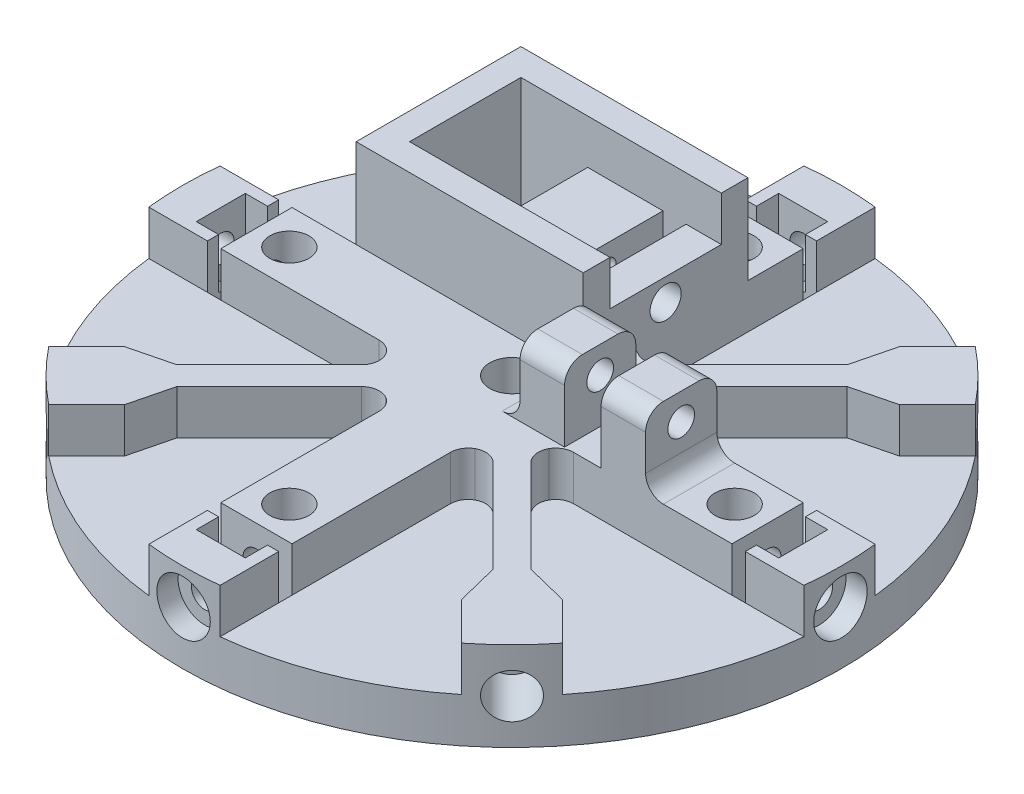
SolidWorks part; units mm, degrees
material "Custom Plastic"
ref_plane "Front Plane" through (0, 0, 0) normal (0, 0, 1) x (1, 0, 0)
ref_plane "Top Plane" through (0, 0, 0) normal (0, 1, 0) x (1, 0, 0)
ref_plane "Right Plane" through (0, 0, 0) normal (1, 0, 0) x (0, 0, -1)
sketch "Sketch1" plane through (0, 0, 0) normal (0, 1, 0) x (1, 0, 0)
  circle A0 centre (0, 0) radius 37
  circle A1 centre (0, 0) radius 2.5
  dimension "D1" = 74
  dimension "D2" = 5
extrude "Boss-Extrude1" add sketch "Sketch1" along normal blind 10
sketch "Sketch5" plane through (0, 10, 0) normal (0, 1, 0) x (1, 0, 0)
  circle A0 centre (0, 0) radius 25 construction
  circle A1 centre (0, 0) radius 37 construction
  point P3 (0, 25)
  point P6 (0, 37)
  point P7 (25, 0)
  point P8 (0, -25)
  point P9 (-25, 0)
  dimension "D1" = 12
  dimension "D2" = 4
hole_wizard "Ø4.0mm Dowel Hole2" positions "Sketch6" profile "Sketch7" hole size "Ø4.0" standard "ANSI Metric"
sketch "Sketch6" plane through (0, 10, 0) normal (0, 1, 0) x (1, 0, 0)
  point P0 (0, 25)
  point P3 (25, 0)
  point P6 (0, -25)
  point P9 (-25, 0)
sketch "Sketch7" plane through (0, 10, -25) normal (1, 0, 0) x (0, 0, 1)
  line L0 (0, 0) -> (0, 9.999)
  line L1 (0, 9.999) -> (2.2, 9.999)
  line L2 (2.2, 9.999) -> (2.2, 0)
  line L5 (2.2, 0) -> (0, 0)
  line L10 (0, 9.999) -> (-2.2, 9.999) construction
  line L11 (0, -6.35) -> (0, 107.95) construction
  dimension "Hole Dia." = 4.4
  dimension "Hole Depth" = 9.999
  dimension "Drill Angle" = 180
ref_plane "Plane1" through (37, 0, 0) normal (1, 0, 0) x (0, 0, -1)
hole_wizard "CBORE for M6 Hex Head Bolt4" positions "Sketch10" profile "Sketch11" counterbore size "M6" standard "ANSI Metric"
sketch "Sketch10" plane through (37, 0, 0) normal (1, 0, 0) x (0, 0, -1)
  point P0 (0, 6)
  dimension "D1" = 6
sketch "Sketch11" plane through (37, 6, 0) normal (0, 1, 0) x (0, 0, -1)
  line L0 (0, 0) -> (0, 11)
  line L1 (0, 11) -> (1.5, 11)
  line L2 (1.5, 11) -> (1.5, 2.5)
  line L3 (1.5, 2.5) -> (3, 2.5)
  line L4 (3, 2.5) -> (3, 0)
  line L5 (3, 0) -> (0, 0)
  line L10 (0, 11) -> (-1.5, 11) construction
  line L11 (0, -6.35) -> (0, 107.95) construction
  dimension "Hole Dia." = 3
  dimension "Hole Depth" = 11
  dimension "C'Bore Dia." = 6
  dimension "C'Bore Depth" = 2.5
  dimension "Drill Angle" = 180
pattern_circular "CirPattern1" count 4 over 360 about axis through (0, 0, 0) along (0, 1, 0) of "CBORE for M6 Hex Head Bolt4"
ref_plane "Plane2" through (26.163, 0, 26.163) normal (0.7071, 0, 0.7071) x (0, -1, 0)
sketch "Sketch18" plane through (26.163, 0, 26.163) normal (0.7071, 0, 0.7071) x (0, -1, 0)
  line L0 (0, 0) -> (-10, 0) construction
  line L1 (-10, 37) -> (-10, -37) construction
  circle A0 centre (-5, 0) radius 2.5
  dimension "D1" = 5
extrude "Cut-Extrude2" cut sketch "Sketch18" against normal blind 6.5
sketch "Sketch19" plane through (0, 10, 0) normal (0, 1, 0) x (1, 0, 0)
  line L0 (-36.7831, -4) -> (-9.6569, -4)
  line L1 (-21.0599, -15.403) -> (-28.838, -23.1812)
  line L2 (-37, 0) -> (0, 0) construction
  line L3 (0, 0) -> (-26.163, -26.163) construction
  line L5 (-4, -36.7831) -> (-4, -9.6569)
  line L7 (-21.0599, -15.403) -> (-15.403, -21.0599)
  line L8 (-15.403, -21.0599) -> (-23.1812, -28.838)
  circle A0 centre (0, 0) radius 37 construction
  arc A1 (-36.7831, -4) -> (-28.838, -23.1812) centre (0, 0) ccw
  arc A2 (-4, -36.7831) -> (-23.1812, -28.838) centre (0, 0) cw
  arc A3 (-9.6569, -4) -> (-4, -9.6569) centre (0, 0) ccw
  point P15 (-18.2314, -18.2314)
  dimension "D1" = 4
  dimension "D2" = 45
  dimension "D3" = 4
  dimension "D4" = 11
extrude "Cut-Extrude3" cut sketch "Sketch19" against normal blind 5
pattern_circular "CirPattern4" count 4 every 90 about axis through (0, 0, 0) along (0, 1, 0) of "Cut-Extrude3"
sketch "Sketch12" plane through (0, 10, 0) normal (0, 1, 0) x (1, 0, 0)
  line L1 (-18.5, 7) -> (-18.5, 19.5)
  line L3 (4, 19.5) -> (4, 7)
  line L4 (-2.55, 7) -> (-2.55, 19.5)
  line L5 (0.05, 7) -> (0.05, 19.5)
  line L6 (-18.5, 19.5) -> (-2.55, 19.5)
  line L7 (4, 19.5) -> (0.05, 19.5)
  line L8 (-2.55, 19.5) -> (0.05, 19.5) construction
  line L9 (-2.55, 7) -> (0.05, 7) construction
  line L10 (0.05, 7) -> (4, 7)
  line L11 (-18.5, 7) -> (-2.55, 7)
  line L12 (4, 13.25) -> (13.5, 13.25) construction
  line L14 (-18.5, 13.25) -> (4, 13.25) construction
  dimension "D1" = 22.5
  dimension "D2" = 15.95
  dimension "D3" = 2.6
  dimension "D4" = 12.5
  dimension "D5" = 9.5
  dimension "D6" = 4
  dimension "D7" = 7
extrude "Boss-Extrude2" add sketch "Sketch12" along normal blind 5 and the other way up to surface other way up to face at (-18.1783, 5, -18.1783)
hole_wizard "CBORE for M5 Hex Head Bolt1" positions "Sketch13" profile "Sketch15" counterbore size "M5" standard "ANSI Metric"
sketch "Sketch13" plane through (4, 0, 0) normal (1, 0, 0) x (0, 0, -1)
  line L0 (13.25, 15) -> (13.25, 10) construction
  line L1 (7, 15) -> (19.5, 15) construction
  line L4 (7, 12.5) -> (19.5, 12.5) construction
  line L5 (7, 15) -> (7, 10) construction
  line L6 (19.5, 15) -> (19.5, 10) construction
  point P0 (13.25, 12.5)
sketch "Sketch15" plane through (4, 12.5, -13.25) normal (0, 1, 0) x (0, 0, -1)
  line L0 (0, 0) -> (0, 12)
  line L1 (0, 12) -> (1, 12)
  line L2 (1, 12) -> (1, 5)
  line L3 (1, 5) -> (1.75, 5)
  line L4 (1.75, 5) -> (1.75, 0)
  line L5 (1.75, 0) -> (0, 0)
  line L10 (0, 12) -> (-1, 12) construction
  line L11 (0, -6.35) -> (0, 107.95) construction
  dimension "Hole Dia." = 2
  dimension "Hole Depth" = 12
  dimension "C'Bore Dia." = 3.5
  dimension "C'Bore Depth" = 5
  dimension "Drill Angle" = 180
sketch "Sketch16" plane through (0, 10, 0) normal (0, 1, 0) x (1, 0, 0)
  line L5 (-18.5, 7) -> (-2.55, 7) construction
  line L11 (4, 4) -> (-21.5, 4)
  line L16 (4, 4) -> (4, 7)
  line L17 (4, 22.5) -> (-21.5, 22.5)
  line L18 (-21.5, 4) -> (-21.5, 22.5)
  line L19 (4, 19.5) -> (0.05, 19.5) construction
  line L20 (-18.5, 19.5) -> (-18.5, 7) construction
  line L21 (4, 19.5) -> (4, 22.5)
  line L22 (4, 19.5) -> (-18.5, 19.5)
  line L24 (4, 7) -> (-18.5, 7)
  line L25 (-18.5, 19.5) -> (-18.5, 7)
  dimension "D1" = 3
  dimension "D2" = 3
  dimension "D3" = 3
extrude "Boss-Extrude3" add sketch "Sketch16" along normal blind 10 and the other way up to surface other way up to face at (-20.3716, 5, -11.3138)
sketch "Sketch17" plane through (0, 15, 0) normal (0, 1, 0) x (1, 0, 0)
  line L2 (-11, 19.5) -> (-11, 7)
  line L3 (4, 36.7831) -> (4, 9.6569) construction
  line L4 (-18.5, 7) -> (-2.55, 7)
  line L5 (-2.55, 7) -> (-2.55, 19.5)
  line L7 (-2.55, 19.5) -> (-18.5, 19.5)
  line L14 (-11, 19.5) -> (-18.5, 19.5)
  line L15 (-18.5, 7) -> (-11, 7)
  line L17 (-18.5, 19.5) -> (-18.5, 7)
  line L18 (-18.5, 19.5) -> (-18.5, 7)
  dimension "D2" = 15
  dimension "D1" = 0
extrude "Cut-Extrude1" cut sketch "Sketch17" against normal up to surface (15 mm away) up to face at (0, 0, -22.8)
pattern_circular "CirPattern2" count 4 over 360 about axis through (0, 0, 0) along (0, 1, 0) of "Cut-Extrude2"
sketch "Sketch21" plane through (0, 5, 0) normal (0, 1, 0) x (1, 0, 0)
  line L0 (-19.2921, -17.1708) -> (-8.3752, -6.2539)
  line L1 (-21.0599, -15.403) -> (-15.403, -21.0599) construction
  line L2 (-21.0599, -15.403) -> (-15.403, -21.0599) construction
  line L3 (-6.2539, -8.3752) -> (-17.1708, -19.2921)
  line L4 (-26.163, -26.163) -> (0, 0) construction
  line L5 (-19.2921, -17.1708) -> (-17.1708, -19.2921)
  line L6 (0, 0) -> (0, -37) construction
  line L7 (19.2921, -17.1708) -> (8.3752, -6.2539)
  line L8 (19.2921, -17.1708) -> (17.1708, -19.2921)
  line L9 (6.2539, -8.3752) -> (17.1708, -19.2921)
  line L10 (0, 0) -> (37, 0) construction
  line L11 (6.2539, 8.3752) -> (17.1708, 19.2921)
  line L12 (19.2921, 17.1708) -> (17.1708, 19.2921)
  line L13 (19.2921, 17.1708) -> (8.3752, 6.2539)
  arc A0 (-9.6569, -4) -> (-4, -9.6569) centre (0, 0) ccw construction
  arc A1 (-28.838, -23.1812) -> (-23.1812, -28.838) centre (0, 0) ccw construction
  arc A2 (-9.6569, -4) -> (-4, -9.6569) centre (0, 0) ccw construction
  arc A3 (-8.3752, -6.2539) -> (-6.2539, -8.3752) centre (0, 0) ccw
  arc A4 (-4, -36.7831) -> (4, -36.7831) centre (0, 0) ccw construction
  arc A5 (8.3752, -6.2539) -> (6.2539, -8.3752) centre (0, 0) cw
  arc A6 (36.7831, -4) -> (36.7831, 4) centre (0, 0) ccw construction
  arc A7 (8.3752, 6.2539) -> (6.2539, 8.3752) centre (0, 0) ccw
  dimension "D1" = 1.5
  dimension "D2" = 3
extrude "Boss-Extrude5" add sketch "Sketch21" along normal up to surface (5 mm away) up to face at (-22.1589, 10, 22.1589)
chamfer "Chamfer1" distance 3 distance2 5 3 edges at (15.403, 7.5, -21.0599) (21.0599, 7.5, 15.403) (-15.403, 7.5, 21.0599)
chamfer "Chamfer2" distance 5 distance2 3 3 edges at (21.0599, 7.5, -15.403) (15.403, 7.5, 21.0599) (-21.0599, 7.5, 15.403)
ref_plane "Plane3" through (0, 0, 28.7) normal (0, 0, 1) x (1, 0, 0)
sketch "Sketch34" plane through (0, 0, 28.7) normal (0, 0, 1) x (1, 0, 0)
  line L0 (4, 5) -> (4, 10)
  line L1 (4, 10) -> (-4, 10)
  line L2 (-4, 10) -> (-4, 5)
  arc A1 (-4, 5) -> (4, 5) centre (0, 6) ccw
extrude "Cut-Extrude8" cut sketch "Sketch34" along normal blind 1.5
pattern_circular "CirPattern7" count 4 over 360 about axis through (0, 0, 0) along (0, 1, 0) of "Cut-Extrude8"
sketch "Sketch36" plane through (0, 0, 30.2) normal (0, 0, -1) x (-1, 0, 0)
  line L2 (-2.75, 10) -> (-2.75, 4.4123)
  line L3 (-2.75, 4.4123) -> (0, 2.8246)
  line L4 (0, 2.8246) -> (2.75, 4.4123)
  line L5 (2.75, 4.4123) -> (2.75, 10)
  line L7 (-4, 10) -> (4, 10) construction
  line L8 (-2.75, 10) -> (2.75, 10)
  line L11 (-1.375, 8.3816) -> (-2.75, 7.5877)
  line L12 (2.75, 7.5877) -> (1.375, 8.3816)
  circle A0 centre (0, 6) radius 2.75 construction
  dimension "D2" = 5.5
  dimension "D1" = 5.5
extrude "Cut-Extrude9" cut sketch "Sketch36" against normal blind 2.5
pattern_circular "CirPattern8" count 4 over 360 about axis through (0, 0, 0) along (0, 1, 0) of "Cut-Extrude9"
sketch "Sketch37" plane through (0, 10, 0) normal (0, 1, 0) x (1, 0, 0)
  line L0 (28.7, -4) -> (9.6569, -4) construction
  line L1 (14, -4) -> (19, -4)
  line L2 (14, -4) -> (14, 4)
  line L3 (14, 4) -> (19, 4)
  line L4 (19, -4) -> (19, 4)
  line L5 (9.6569, 4) -> (28.7, 4) construction
  line L6 (4, 4) -> (4, 7) construction
  dimension "D1" = 5
  dimension "D2" = 10
extrude "Boss-Extrude8" add sketch "Sketch37" along normal blind 8
ref_plane "Plane4" through (11.95, 0, 0) normal (-1, 0, 0) x (0, 0, 1)
fillet "Fillet15" radius 2 11 edges at (6.2539, 7.5, -8.3752) (8.3752, 7.5, -6.2539) (9.6569, 7.5, -4) (9.6569, 7.5, 4) (8.3752, 7.5, 6.2539) (6.2539, 7.5, 8.3752) (4, 7.5, 9.6569) (-8.3752, 7.5, 6.2539) (-9.6569, 7.5, 4) (-4, 7.5, 9.6569) (-6.2539, 7.5, 8.3752)
mirror "Mirror3" about plane through (11.95, 0, 0) normal (-1, 0, 0) of "Boss-Extrude8"
hole_wizard "Ø1.0mm Dowel Hole1" positions "Sketch38" profile "Sketch39" hole size "Ø1.0" standard "ANSI Metric"
sketch "Sketch38" plane through (19, 0, 0) normal (1, 0, 0) x (0, 0, -1)
  line L4 (4, 10) -> (-4, 10) construction
  point P0 (0, 15)
  dimension "D1" = 5
sketch "Sketch39" plane through (19, 15, 0) normal (0, 1, 0) x (0, 0, -1)
  line L0 (0, 0) -> (0, 14.099)
  line L1 (0, 14.099) -> (1.5, 14.099)
  line L2 (1.5, 14.099) -> (1.5, 0)
  line L5 (1.5, 0) -> (0, 0)
  line L10 (0, 14.099) -> (-1.5, 14.099) construction
  line L11 (0, -6.35) -> (0, 107.95) construction
  dimension "Hole Dia." = 3
  dimension "Hole Depth" = 14.099
  dimension "Drill Angle" = 180
fillet "Fillet12" radius 2 6 edges at (19, 10, 0) (16.5, 18, 4) (16.5, 18, -4) (7.4, 18, -4) (7.4, 18, 4) (4.9, 10, 0)
fillet "Fillet16" [suppressed] radius 2
fillet "Fillet13" [suppressed] radius 2
